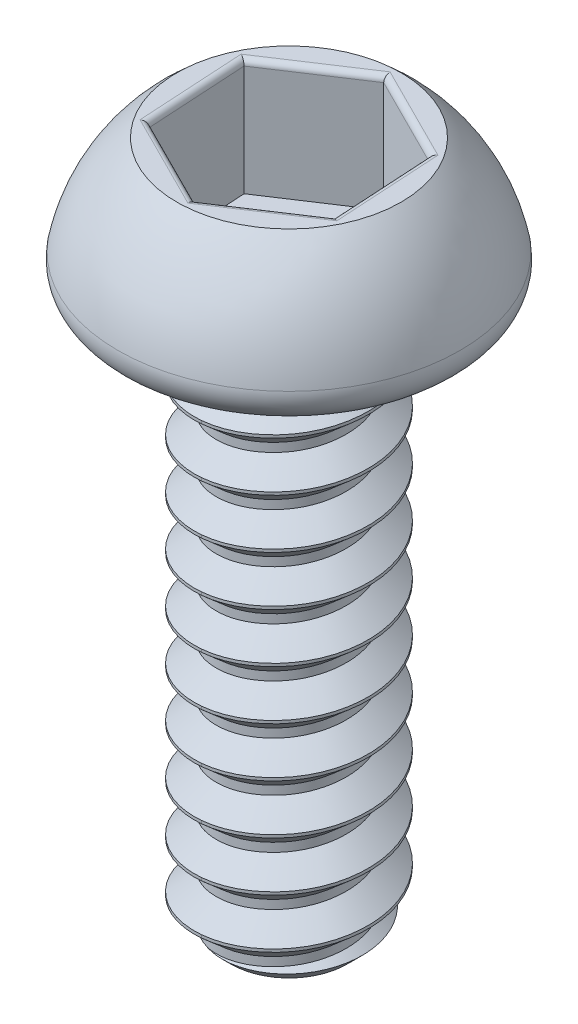
SolidWorks part; units mm, degrees
ref_plane "Piano frontale" through (0, 0, 0) normal (0, 0, 1) x (1, 0, 0)
ref_plane "Piano superiore" through (0, 0, 0) normal (0, 1, 0) x (1, 0, 0)
ref_plane "Piano destro" through (0, 0, 0) normal (1, 0, 0) x (0, 0, -1)
sketch "Schizzo4" plane through (0, 0, 0) normal (0, 0, 1) x (1, 0, 0)
  line L0 (3, 0) -> (1.5, 0)
  line L1 (1.5, 0) -> (1.5, -9.5)
  line L2 (1.5, -9.5) -> (0, -9.5)
  line L3 (0, 4.3167) -> (0, -10.8324) construction
  line L4 (0, 2.3) -> (0, -9.5)
  line L5 (1.9261, 2.3) -> (0, 2.3)
  arc A0 (1.9261, 2.3) -> (3, 0) centre (0, 0) cw
  dimension "D3" = 3
  dimension "D1" = 1.5
  dimension "D2" = 3
  dimension "D4" = 9.5
  dimension "D5" = 2.3
revolve "Rivoluzione1" add sketch "Schizzo4" angle 360 about L3
fillet "Raccordo2" radius 0.5 1 edges at (0, 0, 3)
sketch "Schizzo5" plane through (0, 2.3, 0) normal (0, 1, 0) x (1, 0, 0)
  line L1 (1.5481, -0.7767) -> (1.4467, 0.9524)
  line L2 (1.4467, 0.9524) -> (-0.1014, 1.7291)
  line L3 (-0.1014, 1.7291) -> (-1.5481, 0.7767)
  line L4 (-1.5481, 0.7767) -> (-1.4467, -0.9524)
  line L5 (-1.4467, -0.9524) -> (0.1014, -1.7291)
  line L6 (0.1014, -1.7291) -> (1.5481, -0.7767)
  circle A0 centre (0, 0) radius 1.5 construction
  dimension "D1" = 3
extrude "Taglio-Estrusione1" cut sketch "Schizzo5" against normal blind 2
fillet "Raccordo4" radius 0.1 6 edges at (-0.8248, 2.3, -1.2529) (-1.4974, 2.3, 0.0878) (-0.6726, 2.3, 1.3407) (0.8248, 2.3, 1.2529) (1.4974, 2.3, -0.0878) (0.6726, 2.3, -1.3407)
chamfer "Smusso2" distance 0.5 angle 45 1 edges at (0, -9.5, 1.5)
sketch "Schizzo6" plane through (0, -9.5, 0) normal (0, -1, 0) x (1, 0, 0)
  circle A0 centre (0, 0) radius 1.5 construction
  circle A1 centre (0, 0) radius 1.5
curve "Elica/Spirale1" pitch 0.85 height 9.35 radius 1.5 centre (0, -9.5, 0) axis (0, 1, 0) start towards (1, 0, 0)
sketch "Schizzo8" plane through (0, 0, 0) normal (0, 0, 1) x (1, 0, 0)
  line L0 (1.5, -9.5) -> (1.5, -10.3)
  line L1 (1.5, -10.3) -> (1.125, -9.975)
  line L2 (1.125, -9.975) -> (1.125, -9.825)
  line L3 (1.125, -9.825) -> (1.5, -9.5)
  line L4 (1.5, -9.9) -> (1.125, -9.9) construction
  line L5 (1.5, -9) -> (1.5, 0) construction
  dimension "D1" = 0.375
  dimension "D2" = 0.8
  dimension "D3" = 0.15
sweep "Taglia-Sweep1" cut profiles "Schizzo8" path "Elica/Spirale1" align with end faces yes
sketch "Schizzo9" plane through (0, 0, 0) normal (0, 0, 1) x (1, 0, 0)
  line L4 (1.125, -0.625) -> (1.5, -0.95)
  line L5 (1.5, -0.95) -> (1.5, -0.15)
  line L7 (1.125, -0.475) -> (1.125, -0.625)
  line L9 (1.5, -0.95) -> (1.5, -0.15)
  line L11 (1.125, -0.475) -> (1.125, -0.625)
  line L16 (1.125, -0.625) -> (1.5, -0.95)
  line L18 (1.5, -0.15) -> (1.125, -0.475)
  line L20 (1.5, -0.15) -> (1.125, -0.475)
  dimension "D1" = 0
extrude "Taglio-Estrusione2" cut sketch "Schizzo9" against normal blind 10
